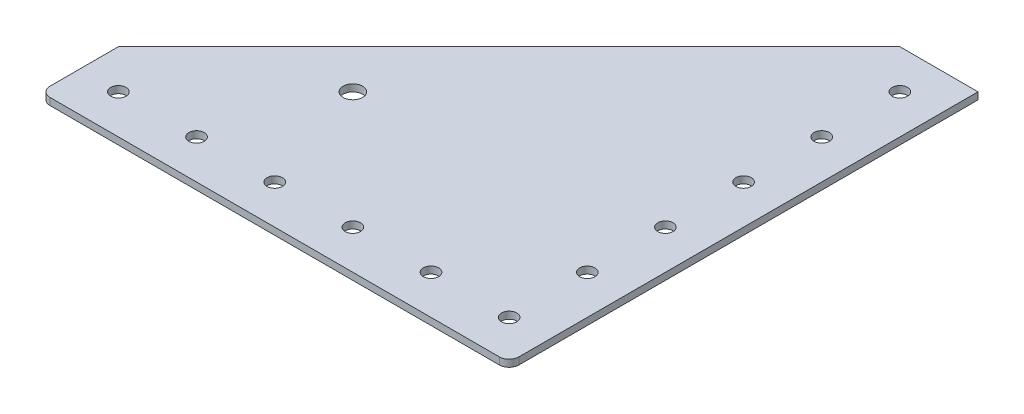
SolidWorks part; units mm, degrees
ref_plane "Front Plane" through (0, 0, 0) normal (0, 0, 1) x (1, 0, 0)
ref_plane "Top Plane" through (0, 0, 0) normal (0, 1, 0) x (1, 0, 0)
ref_plane "Right Plane" through (0, 0, 0) normal (1, 0, 0) x (0, 0, -1)
sketch "Sketch1" plane through (0, 0, 0) normal (0, 1, 0) x (1, 0, 0)
  line L0 (0, 0) -> (0, 152.4)
  line L1 (0, 152.4) -> (-25.4, 152.4)
  line L2 (-25.4, 152.4) -> (-152.4, 25.4)
  line L3 (-152.4, 25.4) -> (-152.4, 0)
  line L4 (-152.4, 0) -> (0, 0)
  circle A0 centre (-12.7, 12.7) radius 2.4892
  circle A1 centre (-38.1, 12.7) radius 2.4892
  circle A2 centre (-63.5, 12.7) radius 2.4892
  circle A3 centre (-88.9, 12.7) radius 2.4892
  circle A4 centre (-114.3, 12.7) radius 2.4892
  circle A5 centre (-12.7, 38.1) radius 2.4892
  circle A6 centre (-12.7, 63.5) radius 2.4892
  circle A7 centre (-12.7, 88.9) radius 2.4892
  circle A8 centre (-12.7, 114.3) radius 2.4892
  circle A9 centre (-139.7, 12.7) radius 2.4892
  circle A13 centre (-12.7, 139.7) radius 2.4892
  circle A17 centre (-101.6, 50.8) radius 3.175
  dimension "D4" = 12.7
  dimension "D5" = 12.7
  dimension "D11" = 6.35
  dimension "D1" = 152.4
  dimension "D2" = 25.4
  dimension "D3" = 152.4
  dimension "D8" = 101.6
  dimension "D9" = 50.8
  dimension "D10" = 25.4
  dimension "D6" = 6
  dimension "D7" = 6
extrude "Boss-Extrude2" add sketch "Sketch1" along normal mid plane 2.286
fillet "Fillet1" radius 3.175 2 edges at (0, 0, 0) (-152.4, 0, 0)
